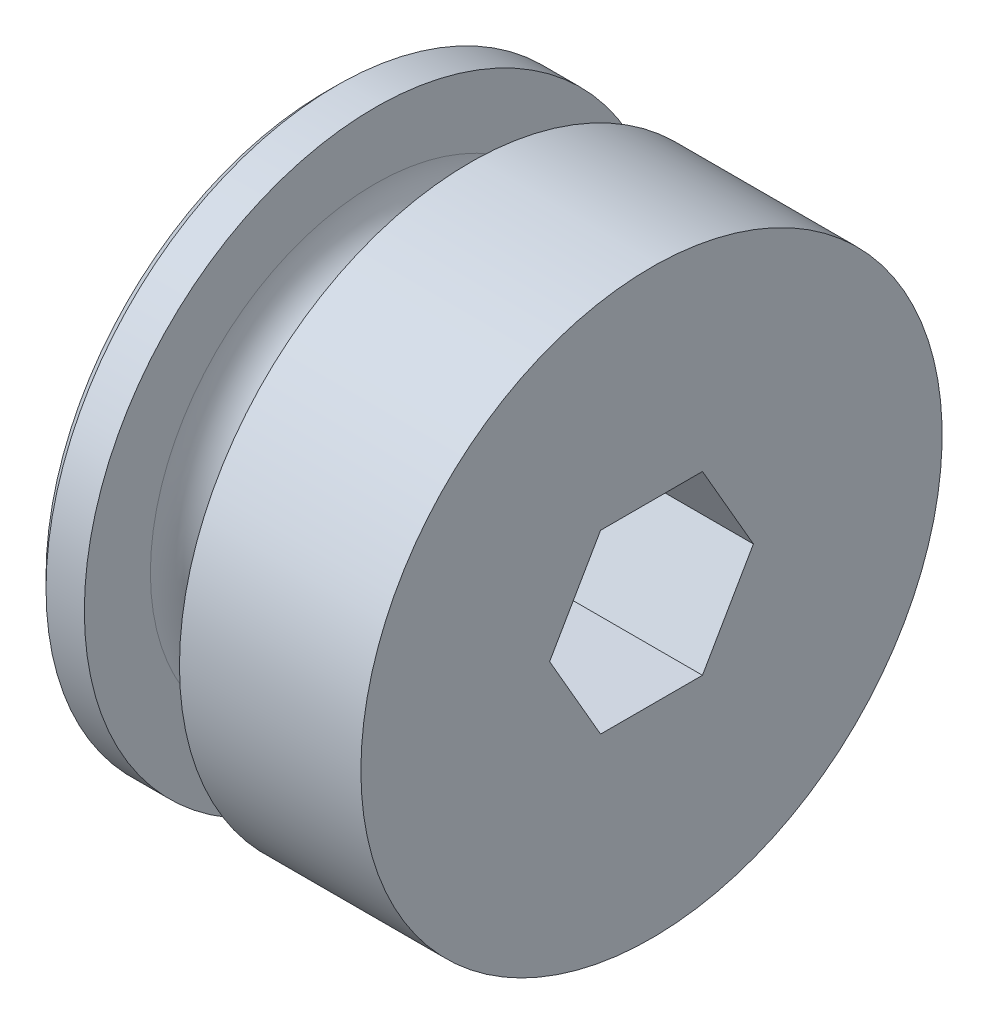
SolidWorks part; units mm, degrees
material "PET"
ref_plane "Front Plane" through (0, 0, 0) normal (0, 0, 1) x (1, 0, 0)
ref_plane "Top Plane" through (0, 0, 0) normal (0, 1, 0) x (1, 0, 0)
ref_plane "Right Plane" through (0, 0, 0) normal (1, 0, 0) x (0, 0, -1)
sketch "Sketch1" plane through (0, 0, 0) normal (0, 0, 1) x (1, 0, 0)
  line L0 (23.495, 0) -> (0, 0)
  line L1 (0, 0) -> (23.495, 0) construction
  line L2 (0, 0) -> (0, 20.955)
  line L3 (0, 20.955) -> (3.556, 20.955)
  line L4 (3.556, 16.1925) -> (3.556, 20.955)
  line L6 (10.414, 16.1925) -> (10.414, 20.955)
  line L7 (10.414, 20.955) -> (23.495, 20.955)
  line L8 (23.495, 0) -> (23.495, 20.955)
  line L9 (6.985, 12.7635) -> (6.985, 0) construction
  arc A0 (3.556, 16.1925) -> (10.414, 16.1925) centre (6.985, 16.1925) ccw
  dimension "D1" = 3.429
  dimension "D2" = 23.495
  dimension "D3" = 20.955
  dimension "D4" = 4.7625
  dimension "D5" = 3.556
  dimension "D7" = 12.7635
revolve "Revolve1" add sketch "Sketch1" angle 360 about L1 region at (12.2994, 9.6998, 0)
chamfer "Chamfer1" distance 0.7937 angle 45 1 edges at (0, 0, 20.955)
sketch "Sketch2" plane through (0, 0, 0) normal (-1, 0, 0) x (0, 0, 1)
  line L1 (3.6735, -6.3627) -> (7.347, 0)
  line L2 (7.347, 0) -> (3.6735, 6.3627)
  line L3 (3.6735, 6.3627) -> (-3.6735, 6.3627)
  line L4 (-3.6735, 6.3627) -> (-7.347, 0)
  line L5 (-7.347, 0) -> (-3.6735, -6.3627)
  line L6 (-3.6735, -6.3627) -> (3.6735, -6.3627)
  circle A0 centre (0, 0) radius 6.3627 construction
  dimension "D1" = 12.7254
extrude "Cut-Extrude1" cut sketch "Sketch2" against normal through all
